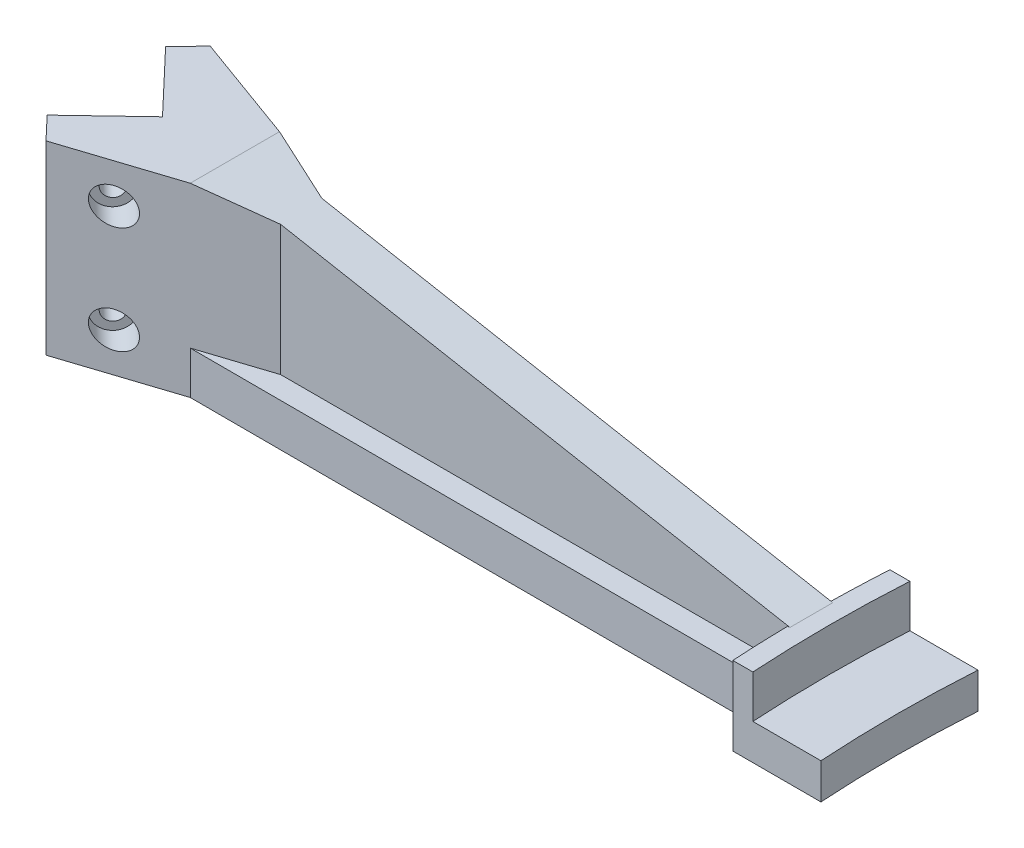
SolidWorks part; units mm, degrees
ref_plane "Front Plane" through (0, 0, 0) normal (0, 0, 1) x (1, 0, 0)
ref_plane "Top Plane" through (0, 0, 0) normal (0, 1, 0) x (1, 0, 0)
ref_plane "Right Plane" through (0, 0, 0) normal (1, 0, 0) x (0, 0, -1)
sketch "Sketch2" plane through (0, 0, 0) normal (0, 1, 0) x (1, 0, 0)
  line L0 (0, 0) -> (-181.1246, 0) construction
  line L1 (0, 0) -> (135.9511, 0) construction
  line L2 (-181.1246, 0) -> (-197.6966, 15.7434)
  line L3 (-197.6966, 15.7434) -> (-191.6108, 22.1496)
  line L4 (-191.6108, 22.1496) -> (-181.1246, 12.1877)
  line L5 (-181.1246, 12.1877) -> (-181.1246, 0)
  line L14 (0.6536, 22) -> (25.3402, 22)
  line L15 (0.6536, -22) -> (25.3402, -22)
  line L16 (25.3402, 22) -> (25.3402, -22) construction
  line L34 (-181.1246, 0) -> (-197.6966, -17.4443)
  line L49 (-197.6966, -17.4443) -> (-191.6108, -23.8504)
  line L50 (-191.6108, -23.8504) -> (-181.1246, -12.8123)
  line L51 (-181.1246, -12.8123) -> (-181.1246, 0)
  line L52 (-181.1246, 12.1877) -> (0.2109, 12.5)
  line L53 (-181.1246, -12.8123) -> (0.2109, -12.5)
  line L54 (0.2109, -12.5) -> (0.2109, 12.5) construction
  line L55 (-181.1246, 12.1877) -> (-181.1246, 24.2548) construction
  line L56 (-181.1246, -12.8123) -> (-181.1246, -19.1381)
  line L58 (-191.6108, 22.1496) -> (-161.1246, 12.2221)
  line L62 (-191.6108, -23.8504) -> (-161.1246, -12.7779)
  line L63 (-161.1246, 12.2221) -> (-161.1246, -12.7779)
  line L64 (-161.1246, -12.7779) -> (-124.8315, 0.4038)
  line L65 (-161.1246, 12.2221) -> (-124.8315, 0.4038)
  arc A0 (0.6536, 22) -> (0.6536, -22) centre (370.6, 0) ccw
  arc A1 (6.2636, 22) -> (6.2636, -22) centre (370.6, 0) ccw
  arc A2 (25.3402, 22) -> (25.3402, -22) centre (370.6, 0) ccw
  point P32 (5.6, 0)
  dimension "D2" = 365
  dimension "D3" = 5.6
  dimension "D4" = 19.04
  dimension "D7" = 25
  dimension "D5" = 133.531
  dimension "D6" = 136.469
  dimension "D8" = 25
  dimension "D9" = 44
  dimension "D10" = 20
  dimension "D18" = 46
  dimension "D19" = 186.7246
extrude "Boss-Extrude2" add sketch "Sketch2" against normal blind 12 contours A0 L52 L53 | L53 L52 | L53 | L52 | A1 L14 A0 L15 | L50 L51 L34 L49 | L5 L4 L3 L2 | L65 L63 L64 region at (-188.0032, 0, -12.1717) region at (-188.0032, 0, 13.1665) region at (-171.1246, 0, 0.2951) region at (-177.9533, 0, -15.5198) region at (-177.9533, 0, 16.4802) region at (-149.0269, 0, 0.0507) region at (-71.8375, 0, 0.1503) region at (3.0196, 0, 0)
extrude "Boss-Extrude3" add sketch "Sketch2<5>" along normal blind 10 from surface contours A2 L14 A1 L15 region at (15.3473, 0, 0) starting at face at (-97.5736, -12, 0.3044)
sketch "Sketch2<5>" plane through (0, 0, 0) normal (0, 1, 0) x (1, 0, 0) same geometry as "Sketch2"
extrude "Boss-Extrude4" add sketch "Sketch2<6>" along normal blind 22 from surface contours A1 L14 A0 L15 region at (3.0196, 0, 0) starting at face at (-94.6416, -12, 0.3044)
sketch "Sketch2<6>" plane through (0, 0, 0) normal (0, 1, 0) x (1, 0, 0) same geometry as "Sketch2"
extrude "Boss-Extrude7" add sketch "Sketch2<9>" along normal blind 40 contours L63 L52 L5 L51 L53 | L5 L4 L3 L2 | L58 L4 L52 | L50 L51 L34 L49 | L50 L62 L53 | L65 L63 L64 region at (-188.0032, 0, -12.1717) region at (-188.0032, 0, 13.1665) region at (-171.1246, 0, 0.2951) region at (-177.9533, 0, -15.5198) region at (-177.9533, 0, 16.4802) region at (-149.0269, 0, 0.0507)
sketch "Sketch2<9>" plane through (0, 0, 0) normal (0, 1, 0) x (1, 0, 0) same geometry as "Sketch2"
sketch "Sketch4" plane through (0, 0, 0) normal (0, 0, 1) x (1, 0, 0)
  line L2 (-197.6966, -12) -> (-197.6966, 40) construction
  line L5 (0.6536, 10) -> (-161.1246, 40)
  line L6 (-191.6108, 40) -> (-124.8315, 40) construction
  line L8 (-181.1246, 0) -> (0.2109, 0) construction
  line L9 (-161.1246, 0) -> (0.6536, 0)
  line L10 (0.6536, 0) -> (0.6536, 10)
  line L11 (0.6536, -12) -> (0.6536, 10) construction
  line L12 (0.6536, 10) -> (0, 10) construction
  line L13 (-161.1246, 40) -> (-161.1246, 0)
  dimension "D1" = 36.572
extrude "Boss-Extrude17" add sketch "Sketch4" along normal blind 6 and the other way blind 6
sketch "Sketch5" plane through (0, 0, 0) normal (0, 0, 1) x (1, 0, 0)
  line L0 (0.6536, 10) -> (-161.1246, 40) construction
  line L1 (0.6536, 10) -> (-161.1246, 40)
extrude "Cut-Extrude-Thin1" cut sketch "Sketch5" against normal through all and the other way through all thin contours L1 thin type one direction wall 10
sketch "Sketch6" plane through (-95.2035, 0, -90.4433) normal (-0.725, 0, -0.6887) x (-0.6887, 0, 0.725)
  line L0 (134.7494, 29) -> (134.7494, -1) construction
  line L1 (124.7494, 40) -> (148.8105, 40) construction
  line L2 (124.7494, 40) -> (144.7494, 40)
  line L3 (124.7494, 40) -> (124.7494, -12)
  line L4 (124.7494, -12) -> (144.7494, -12)
  line L5 (144.7494, 40) -> (144.7494, -12)
  line L6 (124.7494, 40) -> (144.7494, -12) construction
  line L7 (124.7494, -12) -> (144.7494, 40) construction
  line L8 (124.7494, -12) -> (124.7494, 40) construction
  line L9 (124.7494, -12) -> (148.8105, -12) construction
  circle A0 centre (134.7494, 29) radius 5
  circle A1 centre (134.7494, -1) radius 5
  circle A2 centre (134.7494, 29) radius 2.75
  circle A3 centre (134.7494, -1) radius 2.75
  point P3 (134.7494, 14)
  point P6 (134.7494, 14)
  dimension "D2" = 10
  dimension "D3" = 5.5
  dimension "D1" = 20
  dimension "D4" = 30
extrude "Cut-Extrude1" cut sketch "Sketch6" against normal through all from offset 8 contours A0 | A1 offset against normal yes
extrude "Cut-Extrude2" cut sketch "Sketch6<4>" against normal through all both and the other way through all contours A2 | A3
sketch "Sketch6<4>" plane through (-95.2035, 0, -90.4433) normal (-0.725, 0, -0.6887) x (-0.6887, 0, 0.725) same geometry as "Sketch6"
mirror "Mirror1" about plane through (0, 0, 0) normal (0, 0, 1) of "Cut-Extrude1", "Cut-Extrude2"
mirror "Mirror3" about plane through (0, 0, 0) normal (0, 0, 1) of bodies 120
delete or keep bodies "-1" type delete bodies bodies 120
